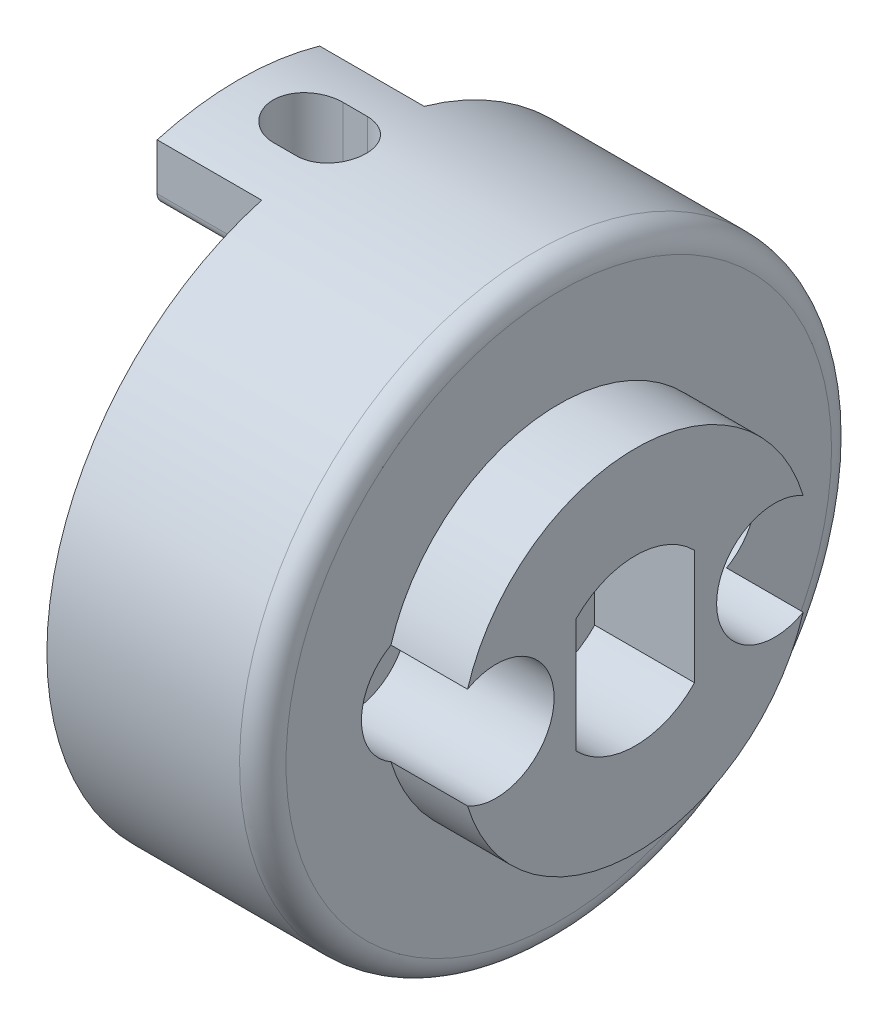
SolidWorks part; units mm, degrees
note: The reader was unsure of these and kept them because the rebuilt part matched: shared geometry of "草图1<3>".
ref_plane "前视基准面" through (0, 0, 0) normal (0, 0, 1) x (1, 0, 0)
ref_plane "上视基准面" through (0, 0, 0) normal (0, 1, 0) x (1, 0, 0)
ref_plane "右视基准面" through (0, 0, 0) normal (1, 0, 0) x (0, 0, -1)
sketch "草图1" plane through (0, 0, 0) normal (1, 0, 0) x (0, 0, -1)
  circle A0 centre (0, 0) radius 9.75
  circle A1 centre (0, 0) radius 12.75
  dimension "D1" = 19.5
  dimension "D2" = 25.5
extrude "凸台-拉伸1" add sketch "草图1" along normal blind 7 contours A1
extrude "凸台-拉伸2" add sketch "草图1<3>" against normal blind 2.3 contours A1 A0
sketch "草图1<3>" plane through (0, 0, 0) normal (1, 0, 0) x (0, 0, -1) same geometry as "草图1"
sketch "草图2" plane through (7, 0, 0) normal (1, 0, 0) x (0, 0, -1)
  line L0 (0, 0) -> (6, 0)
  circle A0 centre (6, 0) radius 1.55
  circle A1 centre (-3, -5.1962) radius 1.55
  circle A2 centre (-3, 5.1962) radius 1.55
  point P10 (0, 0)
  dimension "D2" = 3.1
  dimension "D3" = 3
  dimension "D1" = 6
sketch "草图4" plane through (7, 0, 0) normal (1, 0, 0) x (0, 0, -1)
  line L0 (0, 0) -> (-2.509, -2.5115)
  line L1 (-2.55, 0) -> (-2.55, 2.4698)
  line L2 (-2.55, 0) -> (-2.55, -2.4698)
  line L4 (0, 0) -> (6, 0) construction
  line L5 (2.55, 0) -> (2.55, 2.4698)
  line L6 (2.55, 0) -> (2.55, -2.4698)
  line L7 (0, 0) -> (-0.9205, -3.4286)
  line L9 (-4.0854, -4.0896) -> (-4.0898, -4.0939)
  line L10 (-1.4921, -5.5549) -> (-1.4922, -5.5554)
  line L13 (5.5904, -1.4949) -> (7.2937, -1.9504)
  line L14 (5.5572, 1.4854) -> (7.2939, 1.9496)
  line L16 (-5.5904, -1.4949) -> (-7.2937, -1.9504)
  line L17 (-5.5572, 1.4854) -> (-7.2939, 1.9496)
  circle A0 centre (0, 0) radius 7.55
  arc A1 (-2.55, -2.4698) -> (2.55, -2.4698) centre (0, 0) ccw
  arc A3 (2.55, 2.4698) -> (-2.55, 2.4698) centre (0, 0) ccw
  circle A4 centre (-3, -5.1962) radius 1.55 construction
  circle A5 centre (6, 0) radius 1.55 construction
  circle A8 centre (6, 0) radius 1.55
  circle A10 centre (-6, 0) radius 1.55
  point P38 (0, 0)
  dimension "D1" = 7.1
extrude "凸台-拉伸3" add sketch "草图4" along normal blind 3.3
fillet "圆角1" radius 1 1 edges at (7, 0, -12.75)
sketch "草图5" plane through (7, 0, 0) normal (1, 0, 0) x (0, 0, -1)
  line L0 (5.6535, 1.3048) -> (7.35, 1.7554)
  line L1 (7.35, 1.7554) -> (7.2939, 1.9496)
  line L2 (5.6535, -1.3048) -> (7.35, -1.7595)
  line L3 (7.35, -1.7595) -> (7.2937, -1.9504)
  line L4 (5.6426, 1.5082) -> (7.2939, 1.9496) construction
  line L5 (5.6088, -1.4998) -> (7.2937, -1.9504) construction
  line L6 (5.6426, 1.5082) -> (7.2939, 1.9496)
  line L7 (5.6088, -1.4998) -> (7.2937, -1.9504)
  line L8 (-4.1033, -4.1075) -> (-5.3359, -5.3414)
  line L9 (-3.9567, -4.2437) -> (-5.1988, -5.4855)
  line L10 (-1.5151, -5.6407) -> (-1.9585, -7.2915)
  line L11 (-1.6968, -5.5484) -> (-2.1548, -7.243)
  line L12 (-1.5055, 5.6073) -> (-1.9578, 7.2917)
  line L13 (-1.6968, 5.5484) -> (-2.1512, 7.2451)
  line L14 (-4.1275, 4.1325) -> (-5.3354, 5.3419)
  line L15 (-3.9567, 4.2437) -> (-5.1952, 5.4876)
  line L16 (-4.1033, -4.1075) -> (-5.3359, -5.3414)
  line L17 (-3.9567, -4.2437) -> (-5.1988, -5.4855)
  line L18 (-1.5151, -5.6407) -> (-1.9585, -7.2915)
  line L19 (-1.6968, -5.5484) -> (-2.1548, -7.243)
  line L20 (-5.1988, -5.4855) -> (-5.3359, -5.3414)
  line L21 (-2.1548, -7.243) -> (-1.9585, -7.2915)
  line L22 (-1.5055, 5.6073) -> (-1.9578, 7.2917)
  line L23 (-1.6968, 5.5484) -> (-2.1512, 7.2451)
  line L24 (-4.1275, 4.1325) -> (-5.3354, 5.3419)
  line L25 (-3.9567, 4.2437) -> (-5.1952, 5.4876)
  line L26 (-2.1512, 7.2451) -> (-1.9578, 7.2917)
  line L27 (-5.1952, 5.4876) -> (-5.3354, 5.3419)
  circle A1 centre (6, 0) radius 1.35
  arc A2 (5.6426, 1.5082) -> (5.6088, -1.4998) centre (6, 0) ccw construction
  arc A3 (5.6426, 1.5082) -> (5.6088, -1.4998) centre (6, 0) ccw
  arc A4 (-1.5151, -5.6407) -> (-4.1033, -4.1075) centre (-3, -5.1962) ccw
  circle A5 centre (-3, -5.1962) radius 1.35
  arc A6 (-4.1275, 4.1325) -> (-1.5055, 5.6073) centre (-3, 5.1962) ccw
  circle A7 centre (-3, 5.1962) radius 1.35
  arc A8 (-1.5151, -5.6407) -> (-4.1033, -4.1075) centre (-3, -5.1962) ccw
  circle A9 centre (-3, -5.1962) radius 1.35
  arc A10 (-4.1275, 4.1325) -> (-1.5055, 5.6073) centre (-3, 5.1962) ccw
  circle A11 centre (-3, 5.1962) radius 1.35
  point P38 (0, 0)
  point P61 (0, 0)
  dimension "D1" = 2.7
  dimension "D2" = 3
  dimension "D3" = 3
extrude "凸台-拉伸4" add sketch "草图5" along normal up to surface (3.3 mm away)
sketch "草图6" plane through (7, 0, 0) normal (1, 0, 0) x (0, 0, -1)
  circle A11 centre (6, 0) radius 1.35
  circle A12 centre (-6, 0) radius 1.55
  point P8 (-0.0083, 0)
extrude "切除-拉伸1" cut sketch "草图6" against normal up to next
sketch "草图7" plane through (7, 0, 0) normal (1, 0, 0) x (0, 0, -1)
  line L0 (2.55, -2.4698) -> (2.55, 2.4698) construction
  line L1 (-2.55, 2.4698) -> (-2.55, -2.4698) construction
  line L2 (2.55, -2.4698) -> (2.55, 2.4698)
  line L3 (-2.55, 2.4698) -> (-2.55, -2.4698)
  arc A0 (-2.55, -2.4698) -> (2.55, -2.4698) centre (0, 0) ccw construction
  arc A1 (2.55, 2.4698) -> (-2.55, 2.4698) centre (0, 0) ccw construction
  arc A2 (-2.55, -2.4698) -> (2.55, -2.4698) centre (0, 0) ccw
  arc A3 (2.55, 2.4698) -> (-2.55, 2.4698) centre (0, 0) ccw
extrude "切除-拉伸2" cut sketch "草图7" against normal blind 1
sketch "草图9" plane through (-2.3, 0, 0) normal (-1, 0, 0) x (0, 0, 1)
  line L0 (0, 0) -> (9.75, 0)
  line L1 (-3, 9.75) -> (3, 9.75)
  line L2 (3.5, 10.25) -> (3.5, 12.2602)
  line L3 (-3.5, 10.25) -> (-3.5, 12.2602)
  line L13 (-3, -9.75) -> (3, -9.75)
  line L14 (-3.5, -10.25) -> (-3.5, -12.2602)
  line L15 (3.5, -10.25) -> (3.5, -12.2602)
  circle A0 centre (0, 0) radius 12.75 construction
  circle A1 centre (0, 0) radius 9.75 construction
  arc A2 (3.5, 12.2602) -> (-3.5, 12.2602) centre (0, 0) ccw
  arc A3 (-3, -9.75) -> (-3.5, -10.25) centre (-3, -10.25) ccw
  arc A5 (-3, 9.75) -> (-3.5, 10.25) centre (-3, 10.25) cw
  arc A6 (3.5, 10.25) -> (3, 9.75) centre (3, 10.25) cw
  arc A7 (3.5, -12.2602) -> (-3.5, -12.2602) centre (0, 0) cw
  arc A11 (3.5, -10.25) -> (3, -9.75) centre (3, -10.25) ccw
  point P8 (0, 9.75)
  circle M10 centre (0, 0) radius 12.75
  dimension "D1" = 0.5
extrude "凸台-拉伸5" add sketch "草图9" along normal blind 4.5 contours A6 L2 L3 A5 L1 M10 | L15 A11 L13 A3 L14 M10
ref_plane "基准面2" through (0, 9.75, 0) normal (0, 1, 0) x (1, 0, 0)
sketch "草图16" plane through (0, 9.75, 0) normal (0, 1, 0) x (1, 0, 0)
  line L0 (-2.8, 0) -> (-2.3, 0)
  line L1 (-3.8, 1.5) -> (-2.736, 1.499)
  line L2 (-3.8, -1.5) -> (-2.8463, -1.4996)
  arc A2 (-3.7972, 1.5) -> (-3.7989, -1.5) centre (-3.8, 0) ccw
  arc A3 (-2.8463, -1.4996) -> (-2.8612, 1.4991) centre (-2.8, 0) ccw
extrude "切除-拉伸3" cut sketch "草图16" against normal blind 25 and the other way blind 3
sketch "草图17" plane through (10.3, 0, 0) normal (1, 0, 0) x (0, 0, -1)
  circle A0 centre (-6, 0) radius 2.5
  circle A1 centre (6, 0) radius 2.5
extrude "切除-拉伸4" cut sketch "草图17" against normal blind 6.3
sketch "草图18" plane through (10.3, 0, 0) normal (1, 0, 0) x (0, 0, -1)
  circle A0 centre (0, 0) radius 2.1
extrude "切除-拉伸5" cut sketch "草图18" against normal blind 19
